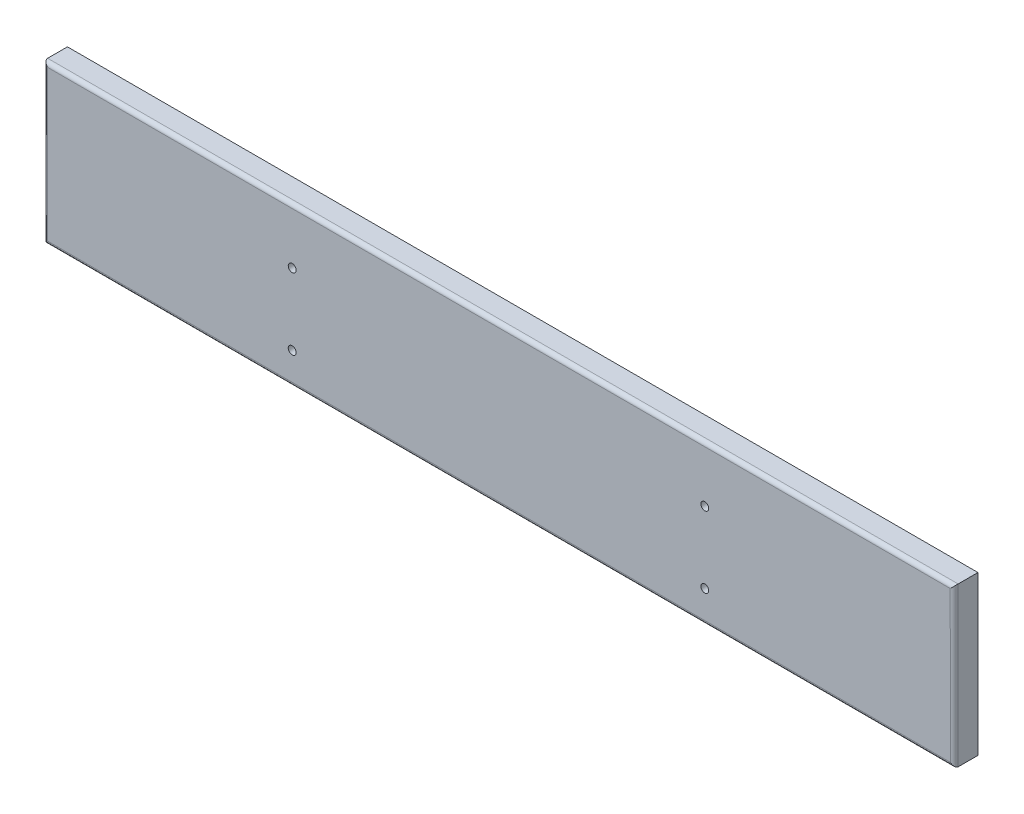
SolidWorks part; units mm, degrees
material "Pine"
ref_plane "Front Plane" through (0, 0, 0) normal (0, 0, 1) x (1, 0, 0)
ref_plane "Top Plane" through (0, 0, 0) normal (0, 1, 0) x (1, 0, 0)
ref_plane "Right Plane" through (0, 0, 0) normal (1, 0, 0) x (0, 0, -1)
sketch "Sketch1" plane through (0, 0, -348.1825) normal (0, 0, 1) x (1, 0, 0)
  line L4 (378.7978, 164.4834) -> (-351.4522, 164.4834)
  line L6 (-351.4522, 37.4834) -> (378.8386, 37.4834)
  line L7 (-351.4522, 164.4834) -> (-351.4522, 37.4834)
  line L8 (378.7978, 164.4834) -> (378.8386, 37.4834)
extrude "Boss-Extrude1" add sketch "Sketch1" along normal blind 19.05 contours L8 L4 L7 L6
hole_wizard "1/4 (0.25) Diameter Hole1" positions "Sketch4" profile "Sketch5" hole size "1/4" standard "ANSI Inch" end condition through all
sketch "Sketch4" plane through (0, 0, -329.1325) normal (0, 0, 1) x (1, 0, 0)
  point P0 (-152.139, 120.0334)
  point P3 (-152.139, 62.8834)
  point P6 (178.7728, 62.8834)
  point P9 (178.7728, 120.0334)
sketch "Sketch5" plane through (-152.139, 120.0334, -329.1325) normal (1, 0, 0) x (0, -1, 0)
  line L0 (0, 0) -> (0, 19.05)
  line L1 (0, 19.05) -> (3.175, 19.05)
  line L2 (3.175, 19.05) -> (3.175, 0)
  line L5 (3.175, 0) -> (0, 0)
  line L11 (0, -6.35) -> (0, 107.95) construction
  dimension "Thru Hole Dia." = 6.35
  dimension "Thru Hole Depth" = 19.05
fillet "Fillet1" radius 3.175 4 edges at (-351.4522, 100.9834, -329.1325) (13.6932, 37.4834, -329.1325) (378.8182, 100.9834, -329.1325) (13.6728, 164.4834, -329.1325)
